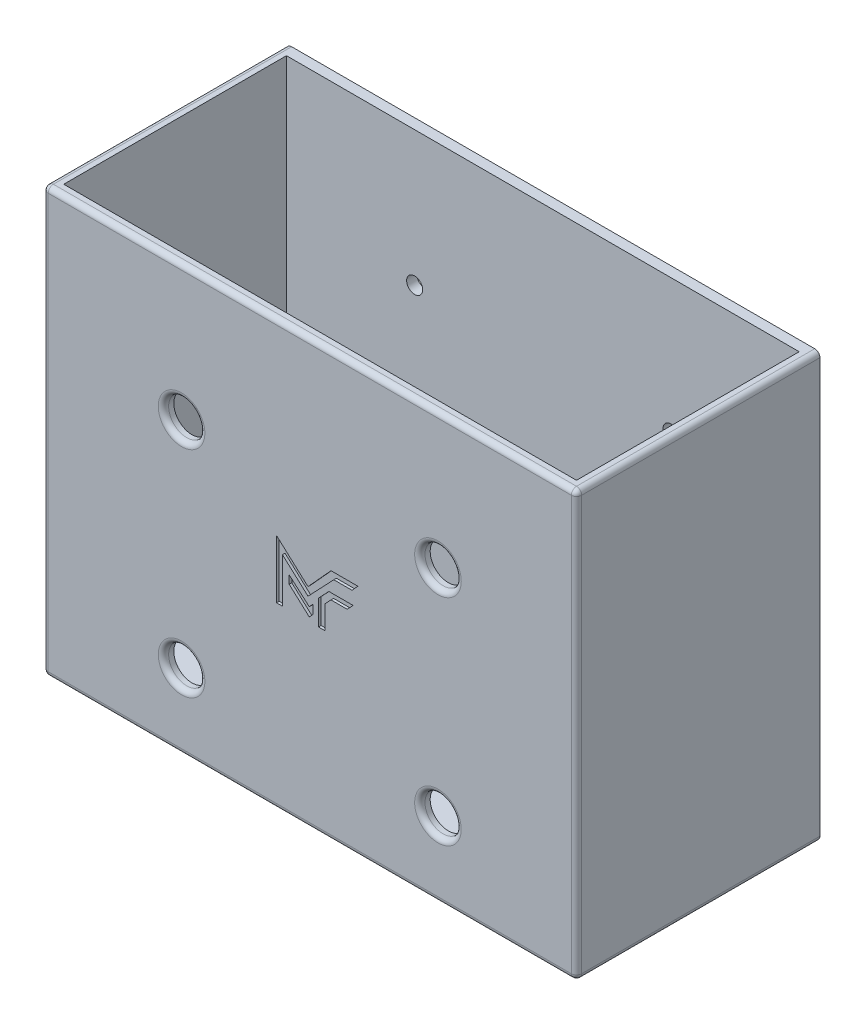
SolidWorks part; units mm, degrees
ref_plane "Plano frontal" through (0, 0, 0) normal (0, 0, 1) x (1, 0, 0)
ref_plane "Plano superior" through (0, 0, 0) normal (0, 1, 0) x (1, 0, 0)
ref_plane "Plano direito" through (0, 0, 0) normal (1, 0, 0) x (0, 0, -1)
sketch "Esboço1" plane through (0, 0, 0) normal (0, 1, 0) x (1, 0, 0)
  line L0 (-51.5, 0) -> (51.5, 0)
  line L1 (51.5, 0) -> (51.5, 47)
  line L2 (51.5, 47) -> (-51.5, 47)
  line L3 (-51.5, 47) -> (-51.5, 0)
  point P4 (0, 0)
  dimension "D1" = 103
  dimension "D2" = 47
extrude "Ressalto-extrusão1" add sketch "Esboço1" against normal blind 2
sketch "Esboço2" plane through (0, 0, 0) normal (0, 1, 0) x (1, 0, 0)
  line L0 (51.5, 47) -> (-51.5, 47) construction
  line L1 (51.5, 47) -> (-51.5, 47)
  line L2 (-51.5, 47) -> (-51.5, 0) construction
  line L3 (-51.5, 47) -> (-51.5, 0)
  line L4 (51.5, 0) -> (51.5, 47) construction
  line L5 (-51.5, 0) -> (51.5, 0) construction
  line L6 (51.5, 0) -> (51.5, 47)
  line L7 (-51.5, 0) -> (51.5, 0)
  line L8 (49.5, 45) -> (-49.5, 45)
  line L9 (-49.5, 45) -> (-49.5, 2)
  line L10 (-49.5, 2) -> (49.5, 2)
  line L11 (49.5, 2) -> (49.5, 45)
  dimension "D1" = 2
extrude "Ressalto-extrusão2" add sketch "Esboço2" along normal blind 80
sketch "Esboço3" plane through (0, 0, -45) normal (0, 0, 1) x (1, 0, 0)
  line L0 (-49.5, 28) -> (49.5, 28)
  line L1 (-49.5, 80) -> (-49.5, 0) construction
  line L2 (49.5, 80) -> (49.5, 0) construction
  line L3 (49.5, 0) -> (-49.5, 0) construction
  line L4 (-49.5, 25) -> (49.5, 25)
  line L5 (-49.5, 28) -> (-49.5, 25)
  line L6 (49.5, 28) -> (49.5, 25)
  dimension "D1" = 28
  dimension "D2" = 3
extrude "Ressalto-extrusão3" add sketch "Esboço3" along normal blind 3
fillet "Filete1" radius 5 1 edges at (0, 25, -45)
sketch "Esboço4" plane through (0, 0, -45) normal (0, 0, 1) x (1, 0, 0)
  line L0 (0, 25) -> (0, 0) construction
  line L1 (-49.5, 25) -> (49.5, 25) construction
  line L2 (0, 12.5) -> (49.5, 12.5) construction
  line L3 (49.5, 20.4174) -> (49.5, 0) construction
  line L4 (0, 28) -> (0, 80) construction
  line L5 (49.5, 28) -> (-49.5, 28) construction
  line L6 (49.5, 80) -> (-49.5, 80) construction
  line L7 (0, 54) -> (49.5, 54) construction
  line L8 (49.5, 20.4174) -> (-49.5, 20.4174) construction
  circle A0 centre (24.75, 12.5) radius 1.55
  circle A1 centre (24.75, 54) radius 1.55
  circle A2 centre (-24.75, 12.5) radius 1.55
  circle A3 centre (-24.75, 54) radius 1.55
  dimension "D1" = 3.1
  dimension "D2" = 24.75
extrude "Corte-extrusão1" cut sketch "Esboço4" against normal blind 3
sketch "Esboço5" plane through (0, 0, 0) normal (0, 0, 1) x (1, 0, 0)
  circle A0 centre (-24.75, 54) radius 3.5
  circle A1 centre (24.75, 54) radius 3.5
  circle A2 centre (-24.75, 12.5) radius 3.5
  circle A3 centre (24.75, 12.5) radius 3.5
  dimension "D1" = 7
extrude "Corte-extrusão2" cut sketch "Esboço5" against normal blind 3
fillet "Filete2" radius 1 4 edges at (28.25, 12.5, 0) (-21.25, 12.5, 0) (28.25, 54, 0) (-21.25, 54, 0)
fillet "Filete3" radius 1 8 edges at (-51.5, 80, -23.5) (0, 80, 0) (51.5, 80, -23.5) (51.5, -2, -23.5) (0, -2, 0) (-51.5, -2, -23.5) (-51.5, 39, 0) (51.5, 39, 0)
sketch "Esboço6" plane through (0, -2, 0) normal (0, -1, 0) x (1, 0, 0)
  line L0 (0, 0) -> (0, -47) construction
  line L1 (50.5, -47) -> (-50.5, -47) construction
  line L2 (0, -23.5) -> (51.5, -23.5) construction
  line L3 (51.5, -1) -> (51.5, -47) construction
  line L4 (12, -23.5) -> (32, -23.5) construction
  line L5 (12, -17.5) -> (32, -17.5)
  line L6 (12, -29.5) -> (32, -29.5)
  line L7 (-12, -23.5) -> (-32, -23.5) construction
  line L8 (-12, -17.5) -> (-32, -17.5)
  line L9 (-12, -29.5) -> (-32, -29.5)
  arc A0 (12, -17.5) -> (12, -29.5) centre (12, -23.5) ccw
  arc A1 (32, -29.5) -> (32, -17.5) centre (32, -23.5) ccw
  arc A2 (-12, -17.5) -> (-12, -29.5) centre (-12, -23.5) cw
  arc A3 (-32, -29.5) -> (-32, -17.5) centre (-32, -23.5) cw
  point P11 (22, -23.5)
  point P16 (0, 0)
  point P19 (-22, -23.5)
  dimension "D1" = 6
  dimension "D2" = 12
  dimension "D3" = 20
extrude "Corte-extrusão3" cut sketch "Esboço6" against normal blind 3
fillet "Filete4" radius 1 16 edges at (22, -2, -17.5) (38, -2, -23.5) (22, -2, -29.5) (-22, -2, -17.5) (-6, -2, -23.5) (-22, -2, -29.5) (6, -2, -23.5) (-38, -2, -23.5) (6, 0, -23.5) (22, 0, -29.5) (38, 0, -23.5) (-38, 0, -23.5) (-22, 0, -29.5) (-6, 0, -23.5) (22, 0, -17.5) (-22, 0, -17.5)
sketch "Esboço7" plane through (0, -2, 0) normal (0, -1, 0) x (1, 0, 0)
  line L0 (0, -12.5) -> (51.5, -12.5) construction
  line L4 (0, 0) -> (0, -47) construction
  line L5 (50.5, -47) -> (-50.5, -47) construction
  line L6 (51.5, -1) -> (51.5, -47) construction
  line L7 (0, -12.5) -> (-51.5, -12.5) construction
  line L8 (-51.5, -47) -> (-51.5, -1) construction
  line L9 (32, -17.5) -> (12, -17.5) construction
  text T0 "<b>      AC</b>"
  text T1 "<b>              DC</b>"
  dimension "D1" = 5
extrude "Corte-extrusão4" cut sketch "Esboço7" against normal blind 0.5
sketch "Logo_MF" plane through (0, 0, 0) normal (0, 0, 1) x (1, 0, 0)
  line L0 (-6.4127, 32.5654) -> (-5.2791, 32.5654)
  line L1 (-5.2791, 32.5654) -> (-5.2791, 41.1853)
  line L2 (-5.2791, 41.1853) -> (-0.3401, 36.6988)
  line L3 (-0.3401, 36.6988) -> (4.643, 41.9417)
  line L4 (4.643, 41.9417) -> (8.1619, 41.9417)
  line L5 (8.1619, 41.9417) -> (9.2898, 43.1834)
  line L6 (9.2898, 43.1834) -> (4.0993, 43.1834)
  line L7 (4.0993, 43.1834) -> (-0.3383, 38.2983)
  line L8 (-0.3383, 38.2983) -> (-6.4127, 43.8161)
  line L9 (-6.4127, 43.8161) -> (-6.4127, 32.5654)
  line L10 (-3.9704, 38.4461) -> (-3.9704, 36.8756)
  line L11 (-3.9704, 36.8756) -> (-0.09, 33.3507)
  line L12 (-0.09, 33.3507) -> (0.5909, 34.1003)
  line L13 (0.5909, 34.1003) -> (0.5909, 35.8204)
  line L14 (0.5909, 35.8204) -> (-0.0911, 35.0696)
  line L15 (-0.0911, 35.0696) -> (-3.9704, 38.4461)
  line L16 (1.6909, 32.5654) -> (1.6909, 37.4075)
  line L17 (1.6909, 37.4075) -> (3.6909, 39.5117)
  line L18 (3.6909, 39.5117) -> (8.3744, 39.5117)
  line L19 (8.3744, 39.5117) -> (7.222, 38.2992)
  line L20 (7.222, 38.2992) -> (4.0998, 38.2992)
  line L21 (4.0998, 38.2992) -> (2.906, 37.0431)
  line L22 (2.906, 37.0431) -> (2.906, 32.5654)
  line L23 (2.906, 32.5654) -> (1.6909, 32.5654)
  line L24 (50.5, -1) -> (50.5, 79) construction
  line L25 (50.5, 79) -> (-50.5, 79) construction
  dimension "D1" = 2.43
  dimension "D2" = 6.97
  dimension "D3" = 1.1
  dimension "D4" = 41.2102
  dimension "D5" = 42.1256
  dimension "D6" = 42.3381
  dimension "D7" = 43.278
  dimension "D8" = 45.857
  dimension "D9" = 46.4002
  dimension "D10" = 46.4007
  dimension "D11" = 46.8091
  dimension "D12" = 47.594
  dimension "D13" = 48.8091
  dimension "D14" = 54.4704
  dimension "D15" = 50.59
  dimension "D16" = 50.5911
  dimension "D17" = 50.8383
  dimension "D18" = 50.8401
  dimension "D19" = 56.9127
  dimension "D20" = 35.1839
  dimension "D21" = 35.8166
  dimension "D22" = 37.8147
  dimension "D23" = 40.5539
  dimension "D24" = 42.1244
  dimension "D25" = 43.1796
  dimension "D26" = 46.4346
extrude "Corte-extrusão5" cut sketch "Logo_MF" against normal blind 0.5
